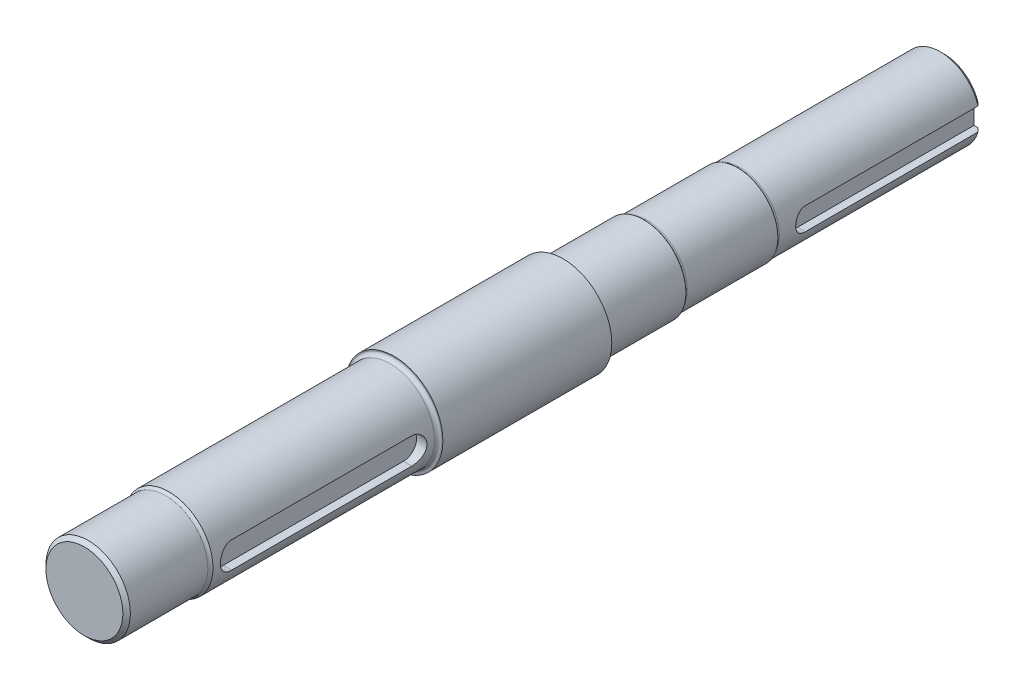
SolidWorks part; units mm, degrees
ref_plane "前视基准面" through (0, 0, 0) normal (0, 0, 1) x (1, 0, 0)
ref_plane "上视基准面" through (0, 0, 0) normal (0, 1, 0) x (1, 0, 0)
ref_plane "右视基准面" through (0, 0, 0) normal (1, 0, 0) x (0, 0, -1)
sketch "草图1" plane through (0, 0, 0) normal (1, 0, 0) x (0, 0, -1)
  line L0 (-440.9955, 0) -> (21608.7816, 0) construction
  line L1 (-165, 0) -> (-165, -22.5)
  line L2 (-165, -22.5) -> (-120, -22.5)
  line L3 (-120, -22.5) -> (-120, -23.5)
  line L4 (-120, -23.5) -> (0, -23.5)
  line L5 (0, -23.5) -> (0, -26)
  line L6 (0, -26) -> (90, -26)
  line L7 (90, -26) -> (90, -23)
  line L8 (90.8, -22.2) -> (91.7, -22.2)
  line L9 (91.7, -22.2) -> (92, -22.5)
  line L10 (92, -22.5) -> (133, -22.5)
  line L11 (133, -22.5) -> (133, -21.5)
  line L12 (133, -21.5) -> (183, -21.5)
  line L13 (183, -21.5) -> (183, -21)
  line L14 (183, -21) -> (293, -21)
  line L15 (293, -21) -> (293, 0)
  line L16 (-165, 0) -> (293, 0)
  arc A0 (90, -23) -> (90.8, -22.2) centre (90.8, -23) cw
  point P20 (90, -22.2)
  dimension "D15" = 0.8
  dimension "D1" = 22.5
  dimension "D2" = 23.5
  dimension "D3" = 26
  dimension "D4" = 21
  dimension "D5" = 21.5
  dimension "D6" = 22.5
  dimension "D7" = 0.3
  dimension "D8" = 2
  dimension "D9" = 45
  dimension "D10" = 120
  dimension "D11" = 43
  dimension "D12" = 458
  dimension "D13" = 110
  dimension "D14" = 50
  dimension "D16" = 135
revolve "旋转1" add sketch "草图1" angle 360 about L0
fillet "圆角1" radius 2 4 edges at (21, 0, -183) (21.5, 0, -133) (23.5, 0, 0) (22.5, 0, 120)
chamfer "倒角1" distance 2 angle 45 2 edges at (21, 0, -293) (22.5, 0, 165)
ref_plane "基准面1" through (18, 0, 0) normal (1, 0, 0) x (0, 0, -1)
sketch "草图3" plane through (18, 0, 0) normal (1, 0, 0) x (0, 0, -1)
  line L0 (-109, 0) -> (-13, 0) construction
  line L1 (-109, 7) -> (-13, 7)
  line L2 (-109, -7) -> (-13, -7)
  line L3 (-120, 23.5) -> (-120, -23.5) construction
  arc A0 (-109, 7) -> (-109, -7) centre (-109, 0) ccw
  arc A1 (-13, -7) -> (-13, 7) centre (-13, 0) ccw
  point P2 (-61, 0)
  point P10 (-116, 0)
  dimension "D2" = 4
extrude "切除-拉伸1" cut sketch "草图3" along normal blind 43
ref_plane "基准面2" through (16, 0, 0) normal (1, 0, 0) x (0, 0, -1)
sketch "草图4" plane through (16, 0, 0) normal (1, 0, 0) x (0, 0, -1)
  line L0 (199, 0) -> (293, 0) construction
  line L1 (293, -19) -> (293, 19) construction
  line L2 (199, 6) -> (293, 6)
  line L3 (199, -6) -> (293, -6)
  line L4 (293, 6) -> (293, -6)
  arc A0 (199, 6) -> (199, -6) centre (199, 0) ccw
  point P4 (246, 0)
extrude "切除-拉伸2" cut sketch "草图4" along normal blind 47
